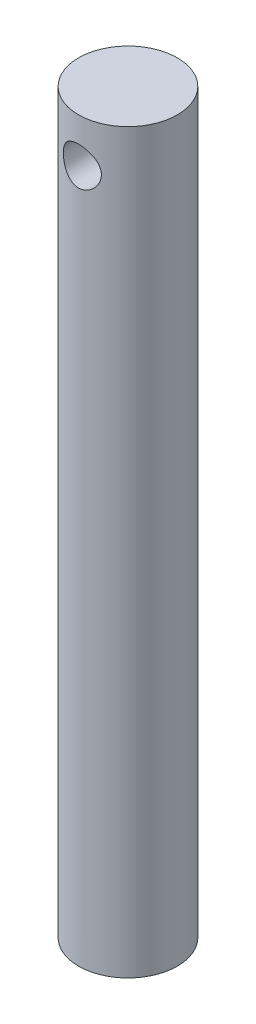
SolidWorks part; units mm, degrees
ref_plane "Front Plane" through (0, 0, 0) normal (0, 0, 1) x (1, 0, 0)
ref_plane "Top Plane" through (0, 0, 0) normal (0, 1, 0) x (1, 0, 0)
ref_plane "Right Plane" through (0, 0, 0) normal (1, 0, 0) x (0, 0, -1)
sketch "Sketch1" plane through (0, 0, 0) normal (0, 1, 0) x (1, 0, 0)
  circle A0 centre (0, 0) radius 9.906
  dimension "D1" = 19.812
extrude "Boss-Extrude1" add sketch "Sketch1" along normal blind 127
sketch "Sketch2" plane through (0, 127, 0) normal (0, 1, 0) x (1, 0, 0)
  circle A0 centre (0, 0) radius 9.906
extrude "Boss-Extrude2" add sketch "Sketch2" along normal blind 20.828
sketch "Sketch3" plane through (0, 0, 0) normal (0, 0, 1) x (1, 0, 0)
  line L0 (9.906, 147.828) -> (-9.906, 147.828) construction
  circle A0 centre (0, 138.938) radius 3.81
  dimension "D2" = 7.62
  dimension "D1" = 8.89
extrude "Cut-Extrude1" cut sketch "Sketch3" against normal blind 15.748 and the other way blind 15.748
